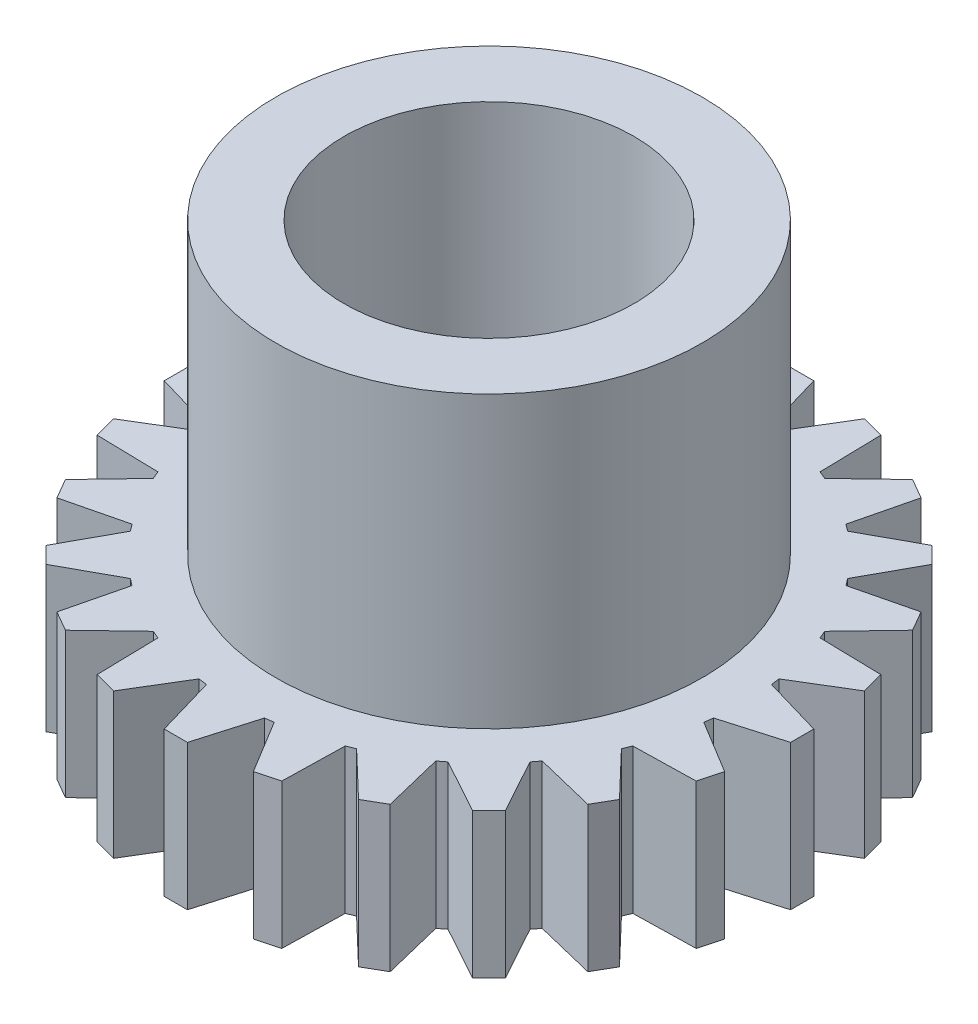
SolidWorks part; units mm, degrees
ref_plane "Front Plane" through (0, 0, 0) normal (0, 0, 1) x (1, 0, 0)
ref_plane "Top Plane" through (0, 0, 0) normal (0, 1, 0) x (1, 0, 0)
ref_plane "Right Plane" through (0, 0, 0) normal (1, 0, 0) x (0, 0, -1)
sketch "Sketch1" plane through (0, 0, 0) normal (0, 1, 0) x (1, 0, 0)
  circle A0 centre (0, 0) radius 3.175
  circle A1 centre (0, 0) radius 4.6672
  dimension "D1" = 6.35
  dimension "D2" = 9.3345
extrude "Boss-Extrude1" add sketch "Sketch1" along normal blind 9.525 contours A1 A0 region at (-4.5352, 0, 0)
sketch "Sketch2" plane through (0, 0, 0) normal (0, 1, 0) x (1, 0, 0)
  line L0 (0, 0) -> (0, 5.588) construction
  line L1 (-0.635, 5.5518) -> (0.635, 5.5518)
  line L2 (0, 5.588) -> (0, 6.858) construction
  line L3 (-0.254, 6.858) -> (0.254, 6.858)
  line L4 (-0.254, 6.858) -> (-0.635, 5.5518)
  line L5 (0.254, 6.858) -> (0.635, 5.5518)
  circle A0 centre (0, 0) radius 5.588
  point P11 (0, 6.858)
  dimension "D1" = 11.176
  dimension "D2" = 1.27
  dimension "D3" = 1.27
  dimension "D4" = 0.508
extrude "Boss-Extrude2" add sketch "Sketch2" along normal blind 3.175 contours L1 A0 region at (0, 0, 0.0017)
extrude "Boss-Extrude3" add sketch "Sketch2<3>" along normal blind 3.175 contours L5 L1 L4 L3
sketch "Sketch2<3>" plane through (0, 0, 0) normal (0, 1, 0) x (1, 0, 0) same geometry as "Sketch2"
pattern_circular "CirPattern1" count 24 over 360 about axis through (0, 9.525, 0) along (0, -1, 0) of "Boss-Extrude3" reverse direction yes
equation "\"Number_Teeth\"= 24"
equation "\"Diametral_Pitch\" = 48"
equation "\"Pitch_Diameter\"= \"Number_Teeth\" * \"1_inch\" / \"Diametral_Pitch\""
equation "\"Tooth_Height\"= .05in"
equation "\"Addendum\"= \"Tooth_Height\" * .4"
equation "\"Dedendum\"= \"Tooth_Height\" * .6"
equation "\"D1@Sketch2\"=\"Pitch_Diameter\"-(2*\"Dedendum\")"
equation "\"D3@Sketch2\"=\"Tooth_Height\""
equation "\"1_inch\"= 1in"
equation "\"D1@CirPattern1\"=\"Number_Teeth\""
